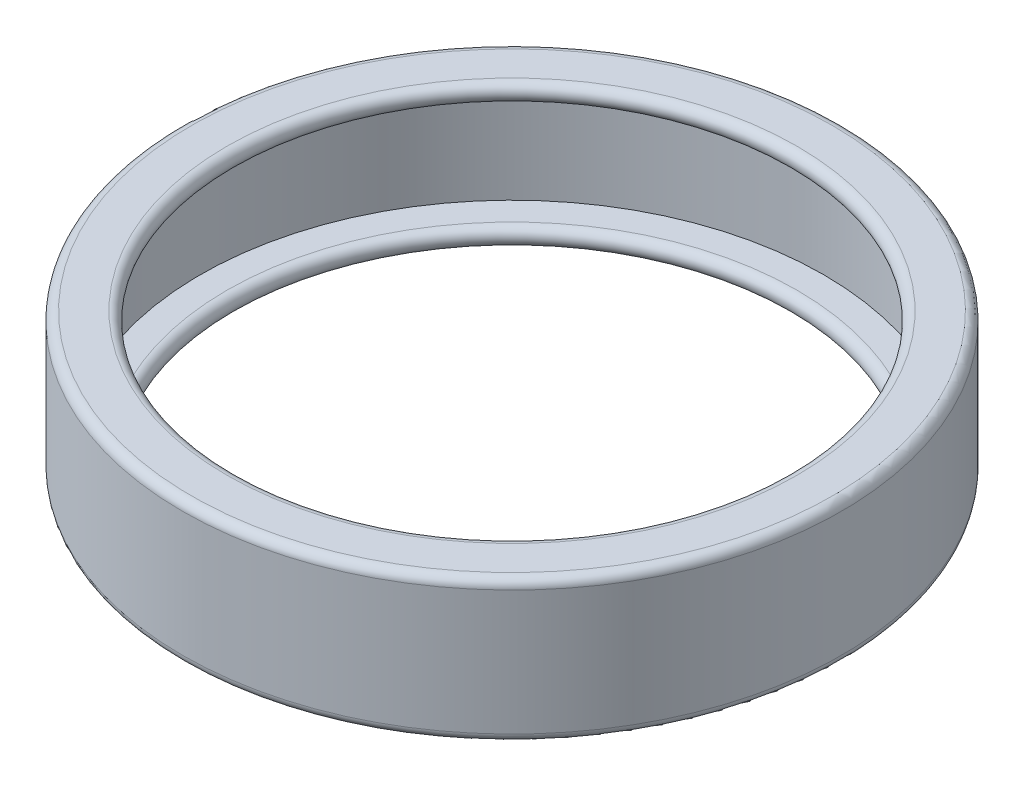
SolidWorks part; units mm, degrees
material "Chrome Stainless Steel"
ref_plane "Front Plane" through (0, 0, 0) normal (1, 0, 0) x (0, 1, 0)
ref_plane "Top Plane" through (0, 0, 0) normal (0, 0, 1) x (0, 1, 0)
ref_plane "Right Plane" through (0, 0, 0) normal (0, 1, 0) x (-1, 0, 0)
sketch "Sketch1" plane through (0, 0, 0) normal (1, 0, 0) x (0, 1, 0)
  line L0 (-15.4469, 0) -> (19.3884, 0) construction
  line L1 (0, 15.4189) -> (0, -15.0382) construction
  line L2 (-4, 15.5) -> (-4, 18.5)
  line L3 (-4, 18.5) -> (4, 18.5)
  line L4 (4, 18.5) -> (4, 15.5)
  line L5 (4, 15.5) -> (3, 15.5)
  line L6 (3, 15.5) -> (3, 17.5)
  line L7 (3, 17.5) -> (-3, 17.5)
  line L8 (-3, 17.5) -> (-3, 15.5)
  line L9 (-3, 15.5) -> (-4, 15.5)
  dimension "D1" = 8
  dimension "D2" = 6
  dimension "D3" = 1
  dimension "D4" = 1
  dimension "D5" = 37
  dimension "D6" = 1
  dimension "D7" = 31
revolve "Revolve1" add sketch "Sketch1" angle 360 about L0
fillet "Fillet1" radius 0.5 2 edges at (0, -4, -18.5) (0, 4, -18.5)
fillet "Fillet2" 2 edges at (0, 4, -15.5) (0, 3, -15.5) type full round first side face at (0, 4, -18) second side face at (0, 3, -15.5) middle face at (0, 4, -15.5)
fillet "Fillet3" 2 edges at (0, -4, -15.5) (0, -3, -15.5) type full round first side face at (0, -4, 18) second side face at (0, -3, -17.5) middle face at (0, -3, -15.5)
ref_axis "Axis1" through (0, 4.4, 0) along (0, -1, 0)
